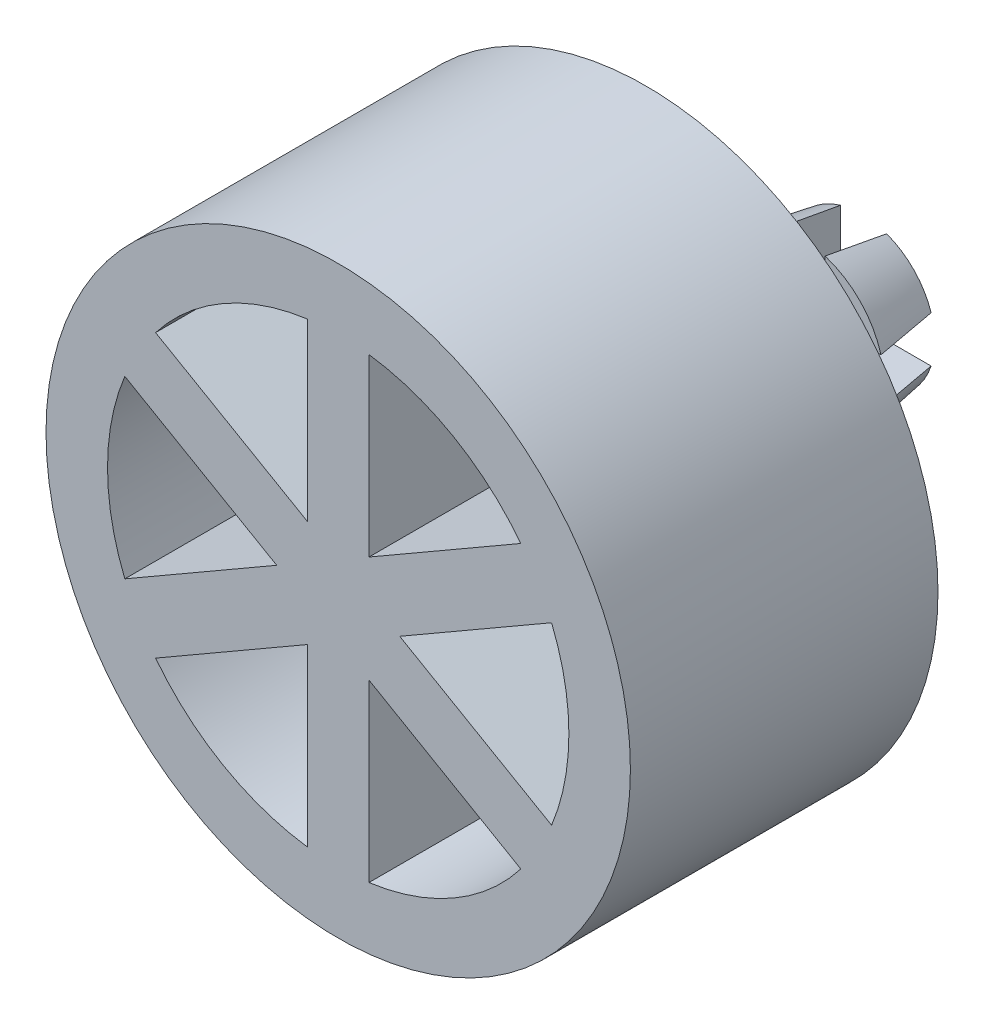
SolidWorks part; units mm, degrees
ref_plane "Płaszczyzna przednia" through (0, 0, 0) normal (0, 0, 1) x (1, 0, 0)
ref_plane "Płaszczyzna górna" through (0, 0, 0) normal (0, 1, 0) x (1, 0, 0)
ref_plane "Płaszczyzna prawa" through (0, 0, 0) normal (1, 0, 0) x (0, 0, -1)
sketch "Szkic1" plane through (0, 0, 0) normal (0, 0, 1) x (1, 0, 0)
  line L0 (-5.9372, -4.5825) -> (-1, -1.7321)
  line L2 (1, -7.433) -> (1, -1.7321)
  line L4 (-1, -7.433) -> (-1, -1.7321)
  line L5 (0.9912, -7.4342) -> (0.2643, -1.9825) construction
  line L6 (0.9912, 7.4342) -> (0.2643, 1.9825) construction
  line L8 (-6.9372, -2.8505) -> (-2, 0)
  line L10 (-6.9372, 2.8505) -> (-2, 0)
  line L12 (-5.9372, 4.5825) -> (-1, 1.7321)
  line L14 (2, 0) -> (6.9372, -2.8505)
  line L15 (-0.2643, -1.9825) -> (-0.9912, -7.4342) construction
  line L19 (-0.2643, 1.9825) -> (-0.9912, 7.4342) construction
  line L21 (1, 1.7321) -> (5.9372, 4.5825)
  line L22 (1, 1.7321) -> (1, 7.433)
  line L23 (2, 0) -> (6.9372, 2.8505)
  line L24 (1, -1.7321) -> (5.9372, -4.5825)
  line L28 (-1, 1.7321) -> (-1, 7.433)
  circle A0 centre (0, 0) radius 2
  circle A1 centre (0, 0) radius 7.5
  circle A2 centre (0, 0) radius 9.5
  point P5 (0, 0)
  point P21 (0, 0)
  dimension "D1" = 4
  dimension "D2" = 15
  dimension "D3" = 2
  dimension "D5" = 3
extrude "Dodanie-wyciągnięcie1" add sketch "Szkic1" along normal blind 10 contours L22 A1 L28 A0 | A0 | L23 A1 L21 A0 | L24 A1 L14 A0 | L4 A1 L2 A0 | L8 A1 L0 A0 | L12 A1 L10 A0 | A2 A1 L21 L23 L14 L24 L2 L4 L0 L8 L10 L12 L28 L22 region at (-4.0659, -2.3475, 0) region at (0, -4.6949, 0) region at (0, 0, 0) region at (-4.0659, 2.3475, 0) region at (4.0659, -2.3475, 0) region at (0, 4.6949, 0) region at (4.0659, 2.3475, 0) region at (-9.2313, 0, 0)
sketch "Szkic2" plane through (0, 0, 0) normal (0, 0, -1) x (-1, 0, 0)
  circle A0 centre (0, 0) radius 2
  dimension "D1" = 4
extrude "Dodanie-wyciągnięcie2" add sketch "Szkic2" along normal blind 5
sketch "Szkic3" plane through (0, 0, -5) normal (0, 0, -1) x (-1, 0, 0)
  circle A0 centre (0, 0) radius 2.75
  dimension "D1" = 5.5
extrude "Dodanie-wyciągnięcie3" add sketch "Szkic3" along normal blind 2 draft 10
sketch "Szkic4" plane through (0, 0, -7) normal (0, 0, -1) x (-1, 0, 0)
  line L1 (0.6699, -8.4237) -> (-0.8301, -8.4237)
  line L2 (0.6699, -8.4237) -> (0.6699, 8.4237)
  line L3 (0.6699, 8.4237) -> (-0.8301, 8.4237)
  line L4 (-0.8301, -8.4237) -> (-0.8301, 8.4237)
  line L5 (0.6699, -8.4237) -> (-0.8301, 8.4237) construction
  line L6 (0.6699, 8.4237) -> (-0.8301, -8.4237) construction
  point P0 (-0.0801, 0)
  point P1 (0, 0)
  dimension "D1" = 0.75
extrude "Wytnij-wyciągnięcie1" cut sketch "Szkic4" against normal up to surface (7 mm away) contours L4 L3 L2 L1 up to face at (0, 0, 0)
sketch "Szkic5" plane through (0, 0, 0) normal (0, 0, -1) x (-1, 0, 0)
  line L1 (11.1845, -0.7508) -> (-11.1614, -0.7508)
  line L2 (11.1845, -0.7508) -> (11.1845, 0.7492)
  line L3 (11.1845, 0.7492) -> (-11.1614, 0.7492)
  line L4 (-11.1614, -0.7508) -> (-11.1614, 0.7492)
  line L5 (11.1845, -0.7508) -> (-11.1614, 0.7492) construction
  line L6 (11.1845, 0.7492) -> (-11.1614, -0.7508) construction
  point P0 (0, 0)
  point P5 (0, 0)
  dimension "D1" = 1.5
extrude "Wytnij-wyciągnięcie2" cut sketch "Szkic5" along normal up to surface (7 mm away) up to face at (-1.5336, 0, -7)
